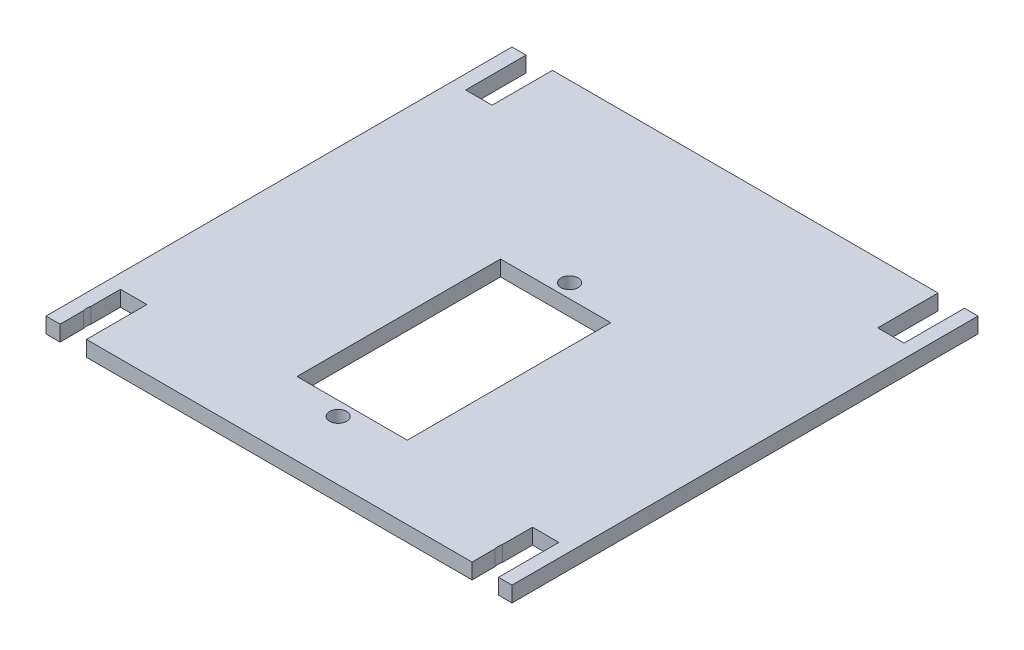
SolidWorks part; units mm, degrees
ref_plane "前视基准面" through (0, 0, 0) normal (0, 0, 1) x (1, 0, 0)
ref_plane "上视基准面" through (0, 0, 0) normal (0, 1, 0) x (1, 0, 0)
ref_plane "右视基准面" through (0, 0, 0) normal (1, 0, 0) x (0, 0, -1)
other "Configuration Table"
sketch "草图1" plane through (0, 0, 0) normal (0, 1, 0) x (1, 0, 0)
  line L0 (30, 0) -> (30, -60) construction
  line L1 (0, 0) -> (60, 0)
  line L2 (0, 0) -> (0, -60)
  line L3 (0, -60) -> (60, -60)
  line L4 (60, 0) -> (60, -60)
  line L6 (22.9, -24.38) -> (37.1, -24.38)
  line L7 (22.9, -24.38) -> (22.9, -50.58)
  line L8 (22.9, -50.58) -> (37.1, -50.58)
  line L9 (37.1, -24.38) -> (37.1, -50.58)
  line L10 (24.1, -19.78) -> (35.9, -19.78)
  line L11 (24.1, -19.78) -> (24.1, -54.78)
  line L12 (24.1, -54.78) -> (35.9, -54.78)
  line L13 (35.9, -19.78) -> (35.9, -54.78)
  circle A0 centre (30, -30) radius 2.4
  circle A1 centre (30, -22.58) radius 1.1
  circle A2 centre (30, -52.38) radius 1.1
  circle A3 centre (3.51, -3.44) radius 1.7
  circle A4 centre (56.56, -3.51) radius 1.7
  circle A5 centre (56.49, -56.56) radius 1.7
  circle A6 centre (3.44, -56.49) radius 1.7
  point P7 (30, -30)
  point P8 (-23.8744, -27.9404)
  point P29 (30, -37.48)
  point P35 (30, -30)
  dimension "D3" = 26.2
  dimension "D9" = 2.2
  dimension "D11" = 2.2
  dimension "D14" = 3.44
  dimension "D1" = 60
  dimension "D2" = 60
  dimension "D4" = 14.2
  dimension "D5" = 5.62
  dimension "D6" = 7.1
  dimension "D7" = 35
  dimension "D8" = 4.6
  dimension "D10" = 29.8
  dimension "D12" = 14.9
  dimension "D13" = 13.1
  dimension "D15" = 3.51
  dimension "D16" = 4
extrude "凸台-拉伸1" add sketch "草图1" along normal blind 2 contours L0 L1 L2 L3 L12 L11 L7 L10 | L1 L0 L10 L13 L9 L12 L3 L4 | L0 L8 L11 L12 A2 | L8 L0 A2 L12 L13 | L0 L10 L11 L6 A1 | L10 L0 A1 L6 L13 region at (46.6493, 0, 28.8736) region at (13.3507, 0, 28.8744) region at (33.137, 0, 22.0423) region at (26.863, 0, 22.0423) region at (26.8437, 0, 52.7049) region at (33.1563, 0, 52.7049)
sketch "草图2" plane through (0, 2, 0) normal (0, 1, 0) x (1, 0, 0)
  line L0 (0, 0) -> (60, 0) construction
  line L5 (1.81, 0) -> (5.21, 0)
  line L6 (1.81, 0) -> (1.81, -7.7762)
  line L7 (1.81, -7.7762) -> (5.21, -7.7762)
  line L8 (5.21, 0) -> (5.21, -7.7762)
  line L9 (60, 0) -> (60, -60) construction
  line L10 (54.86, 0) -> (54.86, -7.7762)
  line L11 (54.86, 0) -> (58.26, 0)
  line L12 (58.26, 0) -> (58.26, -7.7762)
  line L13 (54.86, -7.7762) -> (58.26, -7.7762)
  line L14 (1.81, -52.2238) -> (1.81, -60)
  line L15 (1.81, -52.2238) -> (5.21, -52.2238)
  line L16 (5.21, -52.2238) -> (5.21, -60)
  line L17 (1.81, -60) -> (5.21, -60)
  line L18 (54.86, -52.2238) -> (54.86, -60)
  line L19 (54.86, -60) -> (58.26, -60)
  line L20 (58.26, -52.2238) -> (58.26, -60)
  line L21 (54.86, -52.2238) -> (58.26, -52.2238)
  line L22 (0, -60) -> (60, -60) construction
  circle A0 centre (56.56, -3.51) radius 1.7 construction
  circle A1 centre (3.51, -3.44) radius 1.7 construction
  point P8 (30, -29.9618)
  dimension "D1" = 3.4
  dimension "D2" = 30
  dimension "D3" = 29.9618
  dimension "D4" = 2
  dimension "D5" = 2
extrude "切除-拉伸1" cut sketch "草图2" against normal blind 10
